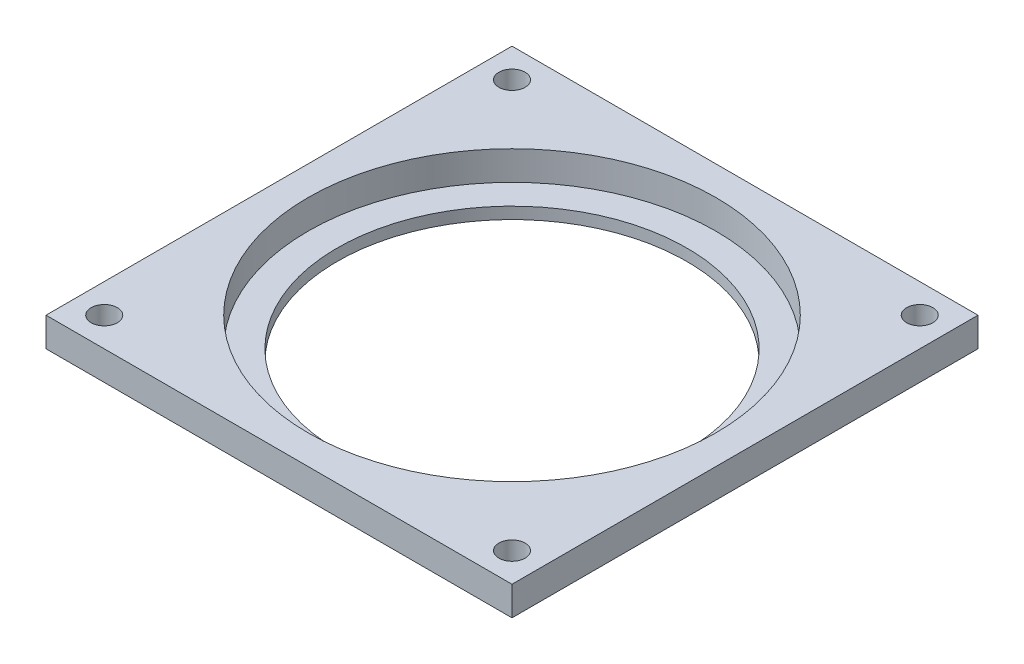
SolidWorks part; units mm, degrees
ref_plane "Front Plane" through (0, 0, 0) normal (0, 0, 1) x (1, 0, 0)
ref_plane "Top Plane" through (0, 0, 0) normal (0, 1, 0) x (1, 0, 0)
ref_plane "Right Plane" through (0, 0, 0) normal (1, 0, 0) x (0, 0, -1)
sketch "Sketch1" plane through (0, 0, 0) normal (0, 1, 0) x (1, 0, 0)
  circle A0 centre (0, 0) radius 35
  circle A1 centre (0, 0) radius 30
extrude "Boss-Extrude1" add sketch "Sketch1" along normal blind 2
sketch "Sketch2" plane through (0, 2, 0) normal (0, 1, 0) x (1, 0, 0)
  line L1 (35, -35) -> (-35, -35)
  line L2 (35, -35) -> (35, 35)
  line L3 (35, 35) -> (-35, 35)
  line L4 (-35, -35) -> (-35, 35)
  line L5 (35, -35) -> (-35, 35) construction
  line L6 (35, 35) -> (-35, -35) construction
  line L7 (40, -40) -> (-40, -40)
  line L8 (40, -40) -> (40, 40)
  line L9 (40, 40) -> (-40, 40)
  line L10 (-40, -40) -> (-40, 40)
  line L11 (40, -40) -> (-40, 40) construction
  line L12 (40, 40) -> (-40, -40) construction
  circle A0 centre (-35, 35) radius 2.25
  circle A1 centre (35, 35) radius 2.25
  circle A2 centre (35, -35) radius 2.25
  circle A3 centre (-35, -35) radius 2.25
  point P0 (0, 0)
  point P6 (0, 0)
  circle M7 centre (0, 0) radius 35
  dimension "D1" = 70
  dimension "D2" = 70
  dimension "D3" = 5
  dimension "D4" = 5
extrude "Boss-Extrude2" add sketch "Sketch2" along normal blind 5 separate body contours L10 L7 L8 L9 A3 L4 A0 L3 A1 L2 A2 L1 | A0 L4 L3 M7 | A1 L3 L2 M7 | A2 L2 L1 M7 | A3 L1 L4 M7 region at (-27.0767, 2, 27.0767) region at (27.0767, 2, 27.0767) region at (-27.0767, 2, -27.0767) region at (27.0767, 2, -27.0767) region at (0, 2, 38.8686)
